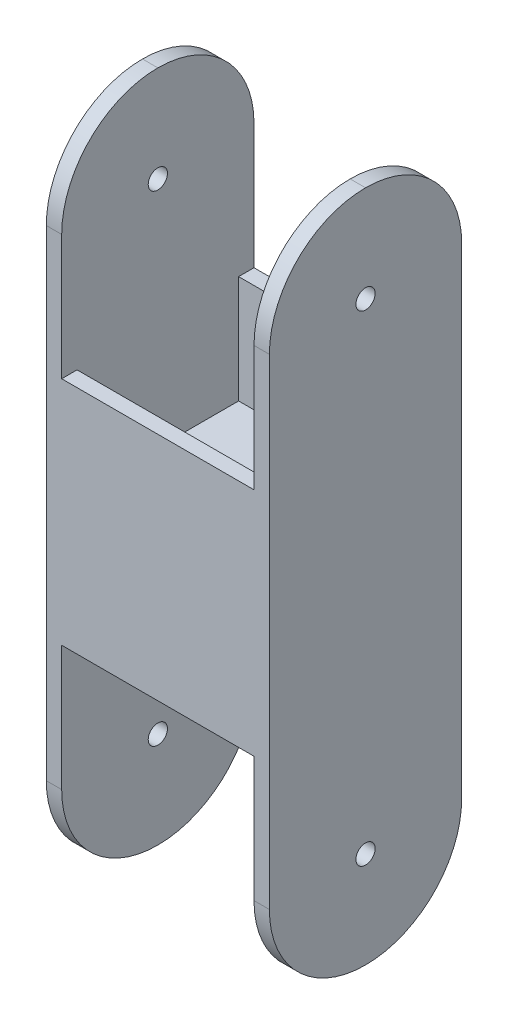
SolidWorks part; units mm, degrees
ref_plane "Front Plane" through (0, 0, 0) normal (0, 0, 1) x (1, 0, 0)
ref_plane "Top Plane" through (0, 0, 0) normal (0, 1, 0) x (1, 0, 0)
ref_plane "Right Plane" through (0, 0, 0) normal (1, 0, 0) x (0, 0, -1)
sketch "Sketch1" plane through (0, 0, 0) normal (0, 0, 1) x (1, 0, 0)
  line L0 (8, -8) -> (8, -171)
  line L1 (0, 0) -> (8, 0)
  line L2 (0, 0) -> (0, -350)
  line L3 (0, -350) -> (8, -350)
  line L4 (116, 0) -> (116, -350)
  line L5 (108, -8) -> (108, -171)
  line L6 (108, 0) -> (116, 0)
  line L7 (108, -350) -> (116, -350)
  line L8 (108, -179) -> (108, -292)
  line L9 (0, 0) -> (8, 0)
  line L10 (0, 0) -> (0, -8)
  line L12 (116, 0) -> (116, -8)
  line L13 (0, -350) -> (8, -350)
  line L14 (0, -350) -> (0, -292)
  line L16 (116, -350) -> (116, -292)
  line L17 (8, -171) -> (108, -171)
  line L18 (0, -146) -> (0, -154)
  line L19 (8, -179) -> (108, -179)
  line L20 (116, -146) -> (116, -154)
  line L21 (8, -179) -> (8, -292)
  line L22 (108, 0) -> (108, -8)
  line L23 (8, 0) -> (8, -8)
  line L24 (108, 0) -> (116, 0)
  line L25 (108, -350) -> (116, -350)
  line L26 (108, -292) -> (108, -350)
  line L27 (8, -292) -> (8, -350)
  dimension "D1" = 171
  dimension "D2" = 100
  dimension "D3" = 8
  dimension "D4" = 8
  dimension "D5" = 171
  dimension "D7" = 8
extrude "Boss-Extrude1" add sketch "Sketch1" along normal blind 100 contours L3 L13 L7 L4 L6 L9 L1 L2 L21 L19 L8 L17 L0 L5 region at (58, -175, 0)
fillet "Fillet1" radius 50 8 edges at (4, 0, 100) (4, 0, 0) (112, -350, 0) (112, -350, 100) (4, -350, 100) (4, -350, 0) (112, 0, 100) (112, 0, 0)
sketch "Sketch2" plane through (116, 0, 0) normal (1, 0, 0) x (0, 0, -1)
  circle A0 centre (-50, -300) radius 5
  circle A1 centre (-50, -50) radius 5
extrude "Cut-Extrude1" cut sketch "Sketch2" against normal blind 116
sketch "Sketch5" plane through (0, 0, 100) normal (0, 0, 1) x (1, 0, 0)
  line L12 (0, -50) -> (0, -300) construction
  line L13 (0, -115) -> (116, -115)
  line L14 (0, -115) -> (0, -235)
  line L15 (0, -235) -> (116, -235)
  line L16 (116, -115) -> (116, -235)
  line L17 (116, -50) -> (116, -300) construction
  line L18 (8, -50) -> (0, -50) construction
  dimension "D1" = 120
  dimension "D2" = 65
extrude "Boss-Extrude4" add sketch "Sketch5" against normal blind 8
sketch "Sketch6" plane through (0, 0, 0) normal (0, 0, -1) x (-1, 0, 0)
  line L9 (-108, -115) -> (-8, -115)
  line L10 (-108, -115) -> (-108, -235)
  line L11 (-108, -235) -> (-8, -235)
  line L12 (-8, -115) -> (-8, -235)
extrude "Boss-Extrude6" add sketch "Sketch6" against normal blind 8
